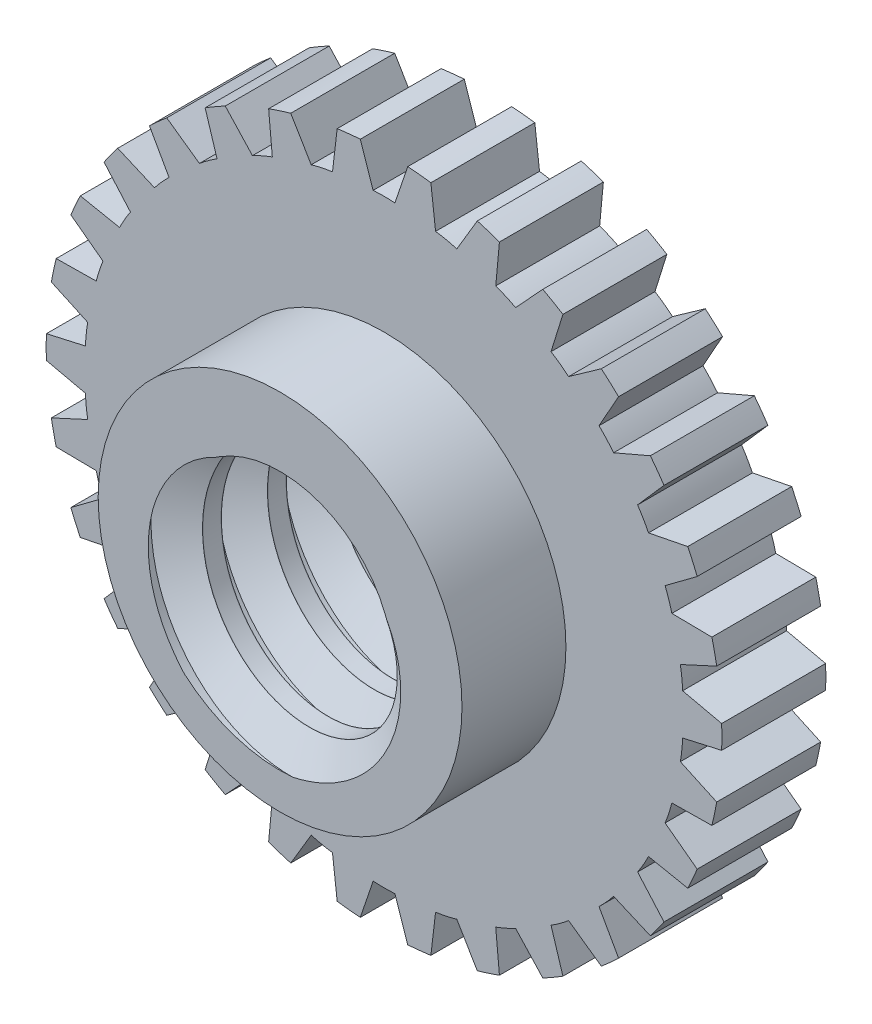
SolidWorks part; units mm, degrees
ref_plane "Ön Düzlem" through (0, 0, 0) normal (0, 0, 1) x (1, 0, 0)
ref_plane "Üst Düzlem" through (0, 0, 0) normal (0, 1, 0) x (1, 0, 0)
ref_plane "Sağ Düzlem" through (0, 0, 0) normal (1, 0, 0) x (0, 0, -1)
sketch "Çizim1" plane through (0, 0, 0) normal (0, 0, 1) x (1, 0, 0)
  circle A0 centre (0, 0) radius 4
  circle A1 centre (0, 0) radius 13
  dimension "D1" = 8
  dimension "D2" = 26
extrude "Yükseklik-Ekstrüzyon1" add sketch "Çizim1" along normal blind 4
sketch "Çizim2" plane through (0, 0, 4) normal (0, 0, 1) x (1, 0, 0)
  circle A1 centre (0, 0) radius 4 construction
  circle A4 centre (0, 0) radius 4
  circle A5 centre (0, 0) radius 7
  dimension "D2" = 14
  dimension "D1" = 3
extrude "Yükseklik-Ekstrüzyon2" add sketch "Çizim2" along normal blind 4
sketch "Çizim3" plane through (0, 0, 0) normal (0, 0, -1) x (-1, 0, 0)
  line L0 (2.8023, 11.1706) -> (3.5895, 12.4946)
  line L3 (0.4185, 11.5091) -> (0.9133, 12.9679)
  line L41 (-0.4185, 11.5091) -> (-0.9133, 12.9679)
  line L100 (0, 11.5237) -> (0, 13.5029) construction
  line L159 (1.9835, 11.3446) -> (1.8029, 12.8744)
  line L160 (5.0635, 10.3438) -> (6.1088, 11.4753)
  line L161 (4.2988, 10.6843) -> (4.4402, 12.2182)
  line L162 (7.1035, 9.065) -> (8.3612, 9.9544)
  line L163 (6.4263, 9.557) -> (6.8835, 11.028)
  line L164 (8.833, 7.39) -> (10.2481, 7.9985)
  line L165 (8.2729, 8.0121) -> (9.0259, 9.3559)
  line L166 (10.1764, 5.3921) -> (11.6872, 5.693)
  line L167 (9.7579, 6.117) -> (10.7739, 7.2749)
  line L168 (11.0751, 3.1584) -> (12.6154, 3.1387)
  line L169 (10.8164, 3.9546) -> (12.051, 4.8759)
  line L170 (11.4898, 0.7868) -> (12.9923, 0.4472)
  line L171 (11.4023, 1.6193) -> (12.8014, 2.2638)
  line L172 (11.4023, -1.6193) -> (12.8014, -2.2638)
  line L173 (11.4898, -0.7868) -> (12.9923, -0.4472)
  line L174 (10.8164, -3.9546) -> (12.051, -4.8759)
  line L175 (11.0751, -3.1584) -> (12.6154, -3.1387)
  line L176 (9.7579, -6.117) -> (10.7739, -7.2749)
  line L177 (10.1764, -5.3921) -> (11.6872, -5.693)
  line L178 (8.2729, -8.0121) -> (9.0259, -9.3559)
  line L179 (8.833, -7.39) -> (10.2481, -7.9985)
  line L180 (6.4263, -9.557) -> (6.8835, -11.028)
  line L181 (7.1035, -9.065) -> (8.3612, -9.9544)
  line L182 (4.2988, -10.6843) -> (4.4402, -12.2182)
  line L183 (5.0635, -10.3438) -> (6.1088, -11.4753)
  line L184 (1.9835, -11.3446) -> (1.8029, -12.8744)
  line L185 (2.8023, -11.1706) -> (3.5895, -12.4946)
  line L186 (-0.4185, -11.5091) -> (-0.9133, -12.9679)
  line L187 (0.4185, -11.5091) -> (0.9133, -12.9679)
  line L188 (-2.8023, -11.1706) -> (-3.5895, -12.4946)
  line L189 (-1.9835, -11.3446) -> (-1.8029, -12.8744)
  line L190 (-5.0635, -10.3438) -> (-6.1088, -11.4753)
  line L191 (-4.2988, -10.6843) -> (-4.4402, -12.2182)
  line L192 (-7.1035, -9.065) -> (-8.3612, -9.9544)
  line L193 (-6.4263, -9.557) -> (-6.8835, -11.028)
  line L194 (-8.833, -7.39) -> (-10.2481, -7.9985)
  line L195 (-8.2729, -8.0121) -> (-9.0259, -9.3559)
  line L196 (-10.1764, -5.3921) -> (-11.6872, -5.693)
  line L197 (-9.7579, -6.117) -> (-10.7739, -7.2749)
  line L198 (-11.0751, -3.1584) -> (-12.6154, -3.1387)
  line L199 (-10.8164, -3.9546) -> (-12.051, -4.8759)
  line L200 (-11.4898, -0.7868) -> (-12.9923, -0.4472)
  line L201 (-11.4023, -1.6193) -> (-12.8014, -2.2638)
  line L202 (-11.4023, 1.6193) -> (-12.8014, 2.2638)
  line L203 (-11.4898, 0.7868) -> (-12.9923, 0.4472)
  line L204 (-10.8164, 3.9546) -> (-12.051, 4.8759)
  line L205 (-11.0751, 3.1584) -> (-12.6154, 3.1387)
  line L206 (-9.7579, 6.117) -> (-10.7739, 7.2749)
  line L207 (-10.1764, 5.3921) -> (-11.6872, 5.693)
  line L208 (-8.2729, 8.0121) -> (-9.0259, 9.3559)
  line L209 (-8.833, 7.39) -> (-10.2481, 7.9985)
  line L210 (-6.4263, 9.557) -> (-6.8835, 11.028)
  line L211 (-7.1035, 9.065) -> (-8.3612, 9.9544)
  line L212 (-4.2988, 10.6843) -> (-4.4402, 12.2182)
  line L213 (-5.0635, 10.3438) -> (-6.1088, 11.4753)
  line L214 (-1.9835, 11.3446) -> (-1.8029, 12.8744)
  line L215 (-2.8023, 11.1706) -> (-3.5895, 12.4946)
  arc A3 (0.9133, 12.9679) -> (-0.9133, 12.9679) centre (0, 5.5237) ccw
  arc A55 (0.4185, 11.5091) -> (-0.4185, 11.5091) centre (0, 5.5237) ccw
  circle A114 centre (0, 0) radius 13 construction
  arc A115 (3.5895, 12.4946) -> (1.8029, 12.8744) centre (1.1484, 5.403) ccw
  arc A116 (2.8023, 11.1706) -> (1.9835, 11.3446) centre (1.1484, 5.403) ccw
  arc A117 (6.1088, 11.4753) -> (4.4402, 12.2182) centre (2.2467, 5.0461) ccw
  arc A118 (5.0635, 10.3438) -> (4.2988, 10.6843) centre (2.2467, 5.0461) ccw
  arc A119 (8.3612, 9.9544) -> (6.8835, 11.028) centre (3.2467, 4.4688) ccw
  arc A120 (7.1035, 9.065) -> (6.4263, 9.557) centre (3.2467, 4.4688) ccw
  arc A121 (10.2481, 7.9985) -> (9.0259, 9.3559) centre (4.1049, 3.6961) ccw
  arc A122 (8.833, 7.39) -> (8.2729, 8.0121) centre (4.1049, 3.6961) ccw
  arc A123 (11.6872, 5.693) -> (10.7739, 7.2749) centre (4.7837, 2.7618) ccw
  arc A124 (10.1764, 5.3921) -> (9.7579, 6.117) centre (4.7837, 2.7618) ccw
  arc A125 (12.6154, 3.1387) -> (12.051, 4.8759) centre (5.2533, 1.7069) ccw
  arc A126 (11.0751, 3.1584) -> (10.8164, 3.9546) centre (5.2533, 1.7069) ccw
  arc A127 (12.9923, 0.4472) -> (12.8014, 2.2638) centre (5.4934, 0.5774) ccw
  arc A128 (11.4898, 0.7868) -> (11.4023, 1.6193) centre (5.4934, 0.5774) ccw
  arc A129 (12.8014, -2.2638) -> (12.9923, -0.4472) centre (5.4934, -0.5774) ccw
  arc A130 (11.4023, -1.6193) -> (11.4898, -0.7868) centre (5.4934, -0.5774) ccw
  arc A131 (12.051, -4.8759) -> (12.6154, -3.1387) centre (5.2533, -1.7069) ccw
  arc A132 (10.8164, -3.9546) -> (11.0751, -3.1584) centre (5.2533, -1.7069) ccw
  arc A133 (10.7739, -7.2749) -> (11.6872, -5.693) centre (4.7837, -2.7618) ccw
  arc A134 (9.7579, -6.117) -> (10.1764, -5.3921) centre (4.7837, -2.7618) ccw
  arc A135 (9.0259, -9.3559) -> (10.2481, -7.9985) centre (4.1049, -3.6961) ccw
  arc A136 (8.2729, -8.0121) -> (8.833, -7.39) centre (4.1049, -3.6961) ccw
  arc A137 (6.8835, -11.028) -> (8.3612, -9.9544) centre (3.2467, -4.4688) ccw
  arc A138 (6.4263, -9.557) -> (7.1035, -9.065) centre (3.2467, -4.4688) ccw
  arc A139 (4.4402, -12.2182) -> (6.1088, -11.4753) centre (2.2467, -5.0461) ccw
  arc A140 (4.2988, -10.6843) -> (5.0635, -10.3438) centre (2.2467, -5.0461) ccw
  arc A141 (1.8029, -12.8744) -> (3.5895, -12.4946) centre (1.1484, -5.403) ccw
  arc A142 (1.9835, -11.3446) -> (2.8023, -11.1706) centre (1.1484, -5.403) ccw
  arc A143 (-0.9133, -12.9679) -> (0.9133, -12.9679) centre (0, -5.5237) ccw
  arc A144 (-0.4185, -11.5091) -> (0.4185, -11.5091) centre (0, -5.5237) ccw
  arc A145 (-3.5895, -12.4946) -> (-1.8029, -12.8744) centre (-1.1484, -5.403) ccw
  arc A146 (-2.8023, -11.1706) -> (-1.9835, -11.3446) centre (-1.1484, -5.403) ccw
  arc A147 (-6.1088, -11.4753) -> (-4.4402, -12.2182) centre (-2.2467, -5.0461) ccw
  arc A148 (-5.0635, -10.3438) -> (-4.2988, -10.6843) centre (-2.2467, -5.0461) ccw
  arc A149 (-8.3612, -9.9544) -> (-6.8835, -11.028) centre (-3.2467, -4.4688) ccw
  arc A150 (-7.1035, -9.065) -> (-6.4263, -9.557) centre (-3.2467, -4.4688) ccw
  arc A151 (-10.2481, -7.9985) -> (-9.0259, -9.3559) centre (-4.1049, -3.6961) ccw
  arc A152 (-8.833, -7.39) -> (-8.2729, -8.0121) centre (-4.1049, -3.6961) ccw
  arc A153 (-11.6872, -5.693) -> (-10.7739, -7.2749) centre (-4.7837, -2.7618) ccw
  arc A154 (-10.1764, -5.3921) -> (-9.7579, -6.117) centre (-4.7837, -2.7618) ccw
  arc A155 (-12.6154, -3.1387) -> (-12.051, -4.8759) centre (-5.2533, -1.7069) ccw
  arc A156 (-11.0751, -3.1584) -> (-10.8164, -3.9546) centre (-5.2533, -1.7069) ccw
  arc A157 (-12.9923, -0.4472) -> (-12.8014, -2.2638) centre (-5.4934, -0.5774) ccw
  arc A158 (-11.4898, -0.7868) -> (-11.4023, -1.6193) centre (-5.4934, -0.5774) ccw
  arc A159 (-12.8014, 2.2638) -> (-12.9923, 0.4472) centre (-5.4934, 0.5774) ccw
  arc A160 (-11.4023, 1.6193) -> (-11.4898, 0.7868) centre (-5.4934, 0.5774) ccw
  arc A161 (-12.051, 4.8759) -> (-12.6154, 3.1387) centre (-5.2533, 1.7069) ccw
  arc A162 (-10.8164, 3.9546) -> (-11.0751, 3.1584) centre (-5.2533, 1.7069) ccw
  arc A163 (-10.7739, 7.2749) -> (-11.6872, 5.693) centre (-4.7837, 2.7618) ccw
  arc A164 (-9.7579, 6.117) -> (-10.1764, 5.3921) centre (-4.7837, 2.7618) ccw
  arc A165 (-9.0259, 9.3559) -> (-10.2481, 7.9985) centre (-4.1049, 3.6961) ccw
  arc A166 (-8.2729, 8.0121) -> (-8.833, 7.39) centre (-4.1049, 3.6961) ccw
  arc A167 (-6.8835, 11.028) -> (-8.3612, 9.9544) centre (-3.2467, 4.4688) ccw
  arc A168 (-6.4263, 9.557) -> (-7.1035, 9.065) centre (-3.2467, 4.4688) ccw
  arc A169 (-4.4402, 12.2182) -> (-6.1088, 11.4753) centre (-2.2467, 5.0461) ccw
  arc A170 (-4.2988, 10.6843) -> (-5.0635, 10.3438) centre (-2.2467, 5.0461) ccw
  arc A171 (-1.8029, 12.8744) -> (-3.5895, 12.4946) centre (-1.1484, 5.403) ccw
  arc A172 (-1.9835, 11.3446) -> (-2.8023, 11.1706) centre (-1.1484, 5.403) ccw
  point P157 (0, 0)
  dimension "D3" = 0.8371
  dimension "D2" = 37.467
  dimension "D1" = 7.5
  dimension "D4" = 30
  dimension "D6" = 1.5404
  dimension "D7" = 1.8265
extrude "Kes-Ekstrüzyon1" cut sketch "Çizim3" against normal blind 4
sketch "Çizim4" plane through (0, 0, 0) normal (0, 0, -1) x (-1, 0, 0)
  circle A0 centre (0, 0) radius 4 construction
  circle A1 centre (0, 0) radius 4
curve "Helis/Spiral1" pitch 2.5 height 8 radius 4 centre (0, 0, 0) axis (0, 0, 1) start towards (-1, 0, 0)
sketch "Çizim5" plane through (0, 0, 0) normal (0, 1, 0) x (1, 0, 0)
  line L0 (-3.8117, 0) -> (-5.6149, 0) construction
  line L1 (-3.8117, -1.6) -> (-4.3549, -1.6)
  line L2 (-5.6149, -0.16) -> (-4.3549, -0.8875)
  line L3 (-3.8117, -1.6) -> (-3.8117, 1.6)
  line L4 (-5.6149, -0.16) -> (-5.6149, 0.16)
  line L5 (-5.6149, 0.16) -> (-4.3549, 0.8875)
  line L6 (-3.8117, 1.6) -> (-4.3549, 1.6)
  line L7 (-4.3549, 1.6) -> (-4.3549, 0.8875)
  line L8 (-4.3549, -0.8875) -> (-4.3549, -1.6)
  line L9 (-3.5895, 0) -> (-4.4402, 0) construction
  dimension "D1" = 3.2
  dimension "D2" = 1.26
  dimension "D3" = 30
  dimension "D4" = 0.32
  dimension "D5" = 0.5432
sweep "Kes-Süpür1" cut profiles "Çizim5" path "Helis/Spiral1" align with end faces yes
